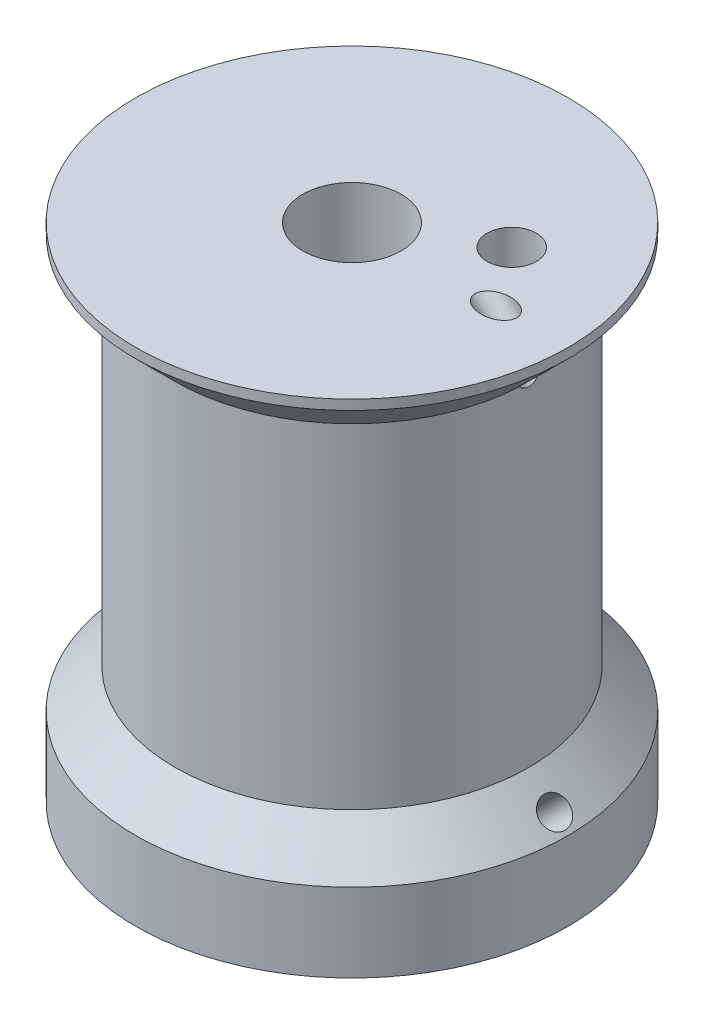
SolidWorks part; units mm, degrees
ref_plane "Front Plane" through (0, 0, 0) normal (0, 0, 1) x (1, 0, 0)
ref_plane "Top Plane" through (0, 0, 0) normal (0, 1, 0) x (1, 0, 0)
ref_plane "Right Plane" through (0, 0, 0) normal (1, 0, 0) x (0, 0, -1)
sketch "Sketch11" plane through (0, 0, 0) normal (0, 0, 1) x (1, 0, 0)
  line L0 (0, 0) -> (0, 25.5) construction
  line L1 (2.5, 25.5) -> (11, 25.5)
  line L2 (11, 25.5) -> (11, 25)
  line L3 (11, 25) -> (9, 23)
  line L4 (9, 23) -> (9, 6)
  line L5 (9, 6) -> (11, 4)
  line L6 (11, 4) -> (11, 0)
  line L7 (11, 0) -> (2.5, 0)
  line L8 (2.5, 0) -> (2.5, 25.5)
  point P11 (10.1942, 5.4226)
  dimension "D1" = 45
  dimension "D2" = 25.5
  dimension "D3" = 18
  dimension "D4" = 22
  dimension "D5" = 4
  dimension "D6" = 17
  dimension "D7" = 5
revolve "Revolve1" add sketch "Sketch11" angle 360 about L0
sketch "Sketch9" plane through (0, 0, 0) normal (0, -1, 0) x (1, 0, 0)
  line L0 (0, 0) -> (5.1529, -2.975) construction
  circle A0 centre (0, 0) radius 2.5 construction
  circle A1 centre (5.1529, -2.975) radius 1.25
  point P5 (5.5028, -2.2631)
  dimension "D1" = 5
  dimension "D2" = 2.5
  dimension "D3" = 2.2
  dimension "D4" = 30
extrude "Cut-Extrude2" cut sketch "Sketch9" against normal through all
sketch "Sketch10" plane through (0, 0, 0) normal (0, 0, 1) x (1, 0, 0)
  line L0 (10.313, 4.687) -> (5.626, 0) construction
  line L1 (10.4157, 22.4073) -> (9.8854, 21.877)
  line L2 (10.4157, 22.4073) -> (6.7927, 26.0303)
  line L3 (10.4157, 22.4073) -> (7.323, 25.5) construction
  line L4 (9.8854, 21.877) -> (6.2624, 25.5)
  line L5 (6.7927, 26.0303) -> (6.2624, 25.5)
  line L6 (11, 4) -> (9, 6) construction
  line L7 (11, 25.5) -> (-11, 25.5) construction
  line L8 (-11, 0) -> (11, 0) construction
  line L9 (8.0739, 23.6885) -> (8.6042, 24.2188) construction
  line L10 (10.1506, 22.1421) -> (6.5275, 25.7652) construction
  line L11 (10.313, 4.687) -> (9.7827, 5.2173)
  line L12 (10.313, 4.687) -> (5.0957, -0.5303)
  line L13 (9.7827, 5.2173) -> (4.5653, 0)
  line L14 (5.0957, -0.5303) -> (4.5653, 0)
  line L15 (7.174, 2.6087) -> (7.7043, 2.0783) construction
  line L16 (10.0478, 4.9522) -> (4.8305, -0.2652) construction
  point P2 (4.7794, 25.5)
  point P60 (8.3391, 23.9537)
  point P84 (7.4392, 2.3435)
  dimension "D1" = 2.6
  dimension "D2" = 3.8
  dimension "D3" = 0.75
  dimension "D4" = 0.75
revolve "Cut-Revolve1" cut sketch "Sketch10" angle 360 about L12 region at (7.4392, 2.3435, 0)
revolve "Cut-Revolve2" cut sketch "Sketch10<3>" angle 360 about L2 region at (8.3391, 23.9537, 0)
sketch "Sketch10<3>" plane through (0, 0, 0) normal (0, 0, 1) x (1, 0, 0) same geometry as "Sketch10"
hole_wizard "M3x0.5 Tapped Hole1" positions "Sketch12" profile "Sketch13" tap size "M3x0.5" standard "ANSI Metric" end condition through all
sketch "Sketch12" plane through (0, 0, 0) normal (1, 0, 0) x (0, 0, -1)
  point P0 (0, 2)
  point P4 (0, 0)
  dimension "D1" = 2
sketch "Sketch13" plane through (0, 2, 0) normal (0, 1, 0) x (0, 0, -1)
  line L0 (0, 0) -> (0, 11)
  line L1 (0, 11) -> (1.25, 11)
  line L2 (1.25, 11) -> (1.25, 0)
  line L5 (1.25, 0) -> (0, 0)
  line L11 (0, -6.35) -> (0, 107.95) construction
  dimension "Thru Tap Drill Dia." = 2.5
  dimension "Thru Tap Drill Depth" = 11
cosmetic thread "Hole Thread1" parameters "D2"=3
